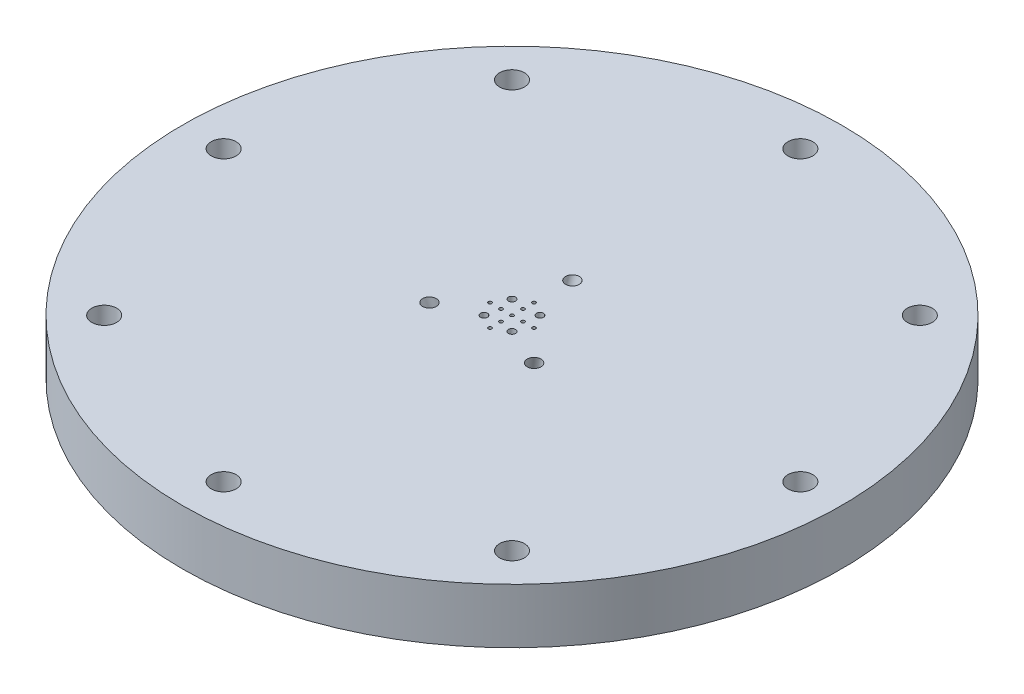
SolidWorks part; units mm, degrees
ref_plane "Front Plane" through (0, 0, 0) normal (0, 0, 1) x (1, 0, 0)
ref_plane "Top Plane" through (0, 0, 0) normal (0, 1, 0) x (1, 0, 0)
ref_plane "Right Plane" through (0, 0, 0) normal (1, 0, 0) x (0, 0, -1)
sketch "Sketch1" plane through (0, 0, 0) normal (0, 1, 0) x (1, 0, 0)
  circle A0 centre (0, 0) radius 38.1
  dimension "D1" = 76.2
extrude "Boss-Extrude1" add sketch "Sketch1" along normal blind 6.35
sketch "Sketch2" plane through (0, 0, 0) normal (0, -1, 0) x (1, 0, 0)
  circle A0 centre (0, 0) radius 33.3375
  circle A1 centre (0, 33.3375) radius 0.762
  dimension "D1" = 66.675
hole_wizard "CBORE for #4 Button Head Cap Screw1" positions "Sketch5" profile "Sketch4" counterbore size "#4" standard "ANSI Inch" end condition through all
sketch "Sketch5" plane through (0, 0, 0) normal (0, -1, 0) x (-1, 0, 0)
  point P0 (0, -33.3375)
sketch "Sketch4" plane through (0, 0, 33.3375) normal (1, 0, 0) x (0, 0, -1)
  line L0 (0, 0) -> (0, 6.35)
  line L1 (0, 6.35) -> (1.4351, 6.35)
  line L3 (1.4351, 6.35) -> (1.4351, 2.794)
  line L4 (1.4351, 2.794) -> (2.413, 2.794)
  line L5 (2.413, 2.794) -> (2.413, 0)
  line L7 (2.413, 0) -> (0, 0)
  line L11 (0, -6.35) -> (0, 107.95) construction
  dimension "Thru Hole Dia." = 2.8702
  dimension "Thru Hole Depth" = 6.35
  dimension "C'Bore Dia." = 4.826
  dimension "C'Bore Depth" = 2.794
pattern_circular "CirPattern1" count 8 over 360 about axis through (0, 0, 0) along (0, 1, 0) of "CBORE for #4 Button Head Cap Screw1"
sketch "Sketch6" plane through (0, 0, 0) normal (0, -1, 0) x (1, 0, 0)
  line L0 (0, -15.5414) -> (0, 14.7731) construction
  line L1 (0, 0) -> (2.6653, -2.6653) construction
  circle A0 centre (0, -2.54) radius 0.1984
  circle A1 centre (0, -1.27) radius 0.1984
  circle A2 centre (0, 0) radius 0.1984
  circle A5 centre (1.6164, -1.6164) radius 0.4083
  circle A6 centre (0, -5.08) radius 0.7938
  dimension "D1" = 0.3969
  dimension "D2" = 0.3969
  dimension "D5" = 0.3969
  dimension "D6" = 0.8166
  dimension "D7" = 2.286
  dimension "D8" = 1.5875
  dimension "D3" = 1.27
  dimension "D4" = 2.54
  dimension "D9" = 5.08
extrude "Cut-Extrude1" cut sketch "Sketch6" against normal through all contours A0 | A1
pattern_circular "CirPattern2" count 4 over 360 about axis through (0, 0, 0) along (0, -1, 0) of "Cut-Extrude1"
extrude "Cut-Extrude2" cut sketch "Sketch6<3>" against normal through all contours A2
sketch "Sketch6<3>" plane through (0, 0, 0) normal (0, -1, 0) x (1, 0, 0) same geometry as "Sketch6"
extrude "Cut-Extrude4" cut sketch "Sketch6<5>" against normal through all contours A5
sketch "Sketch6<5>" plane through (0, 0, 0) normal (0, -1, 0) x (1, 0, 0) same geometry as "Sketch6"
pattern_circular "CirPattern4" count 4 over 360 about axis through (0, 6.35, 0) along (0, -1, 0) of "Cut-Extrude4" reverse direction yes
sketch "Sketch7" plane through (0, 6.35, 0) normal (0, 1, 0) x (1, 0, 0)
  line L0 (0, 15.5414) -> (0, -14.7731) construction
  circle A0 centre (0, 6.985) radius 0.7937
  dimension "D1" = 1.5875
  dimension "D2" = 6.985
sketch3d "3DSketch1"
  line L0 (0, 6.35, -6.985) -> (0, 0, -5.08)
sweep "Cut-Sweep1" cut profiles "Sketch7" path "3DSketch1"
pattern_circular "CirPattern6" count 3 over 360 about axis through (0, 6.35, 0) along (0, -1, 0) of "Cut-Sweep1"
